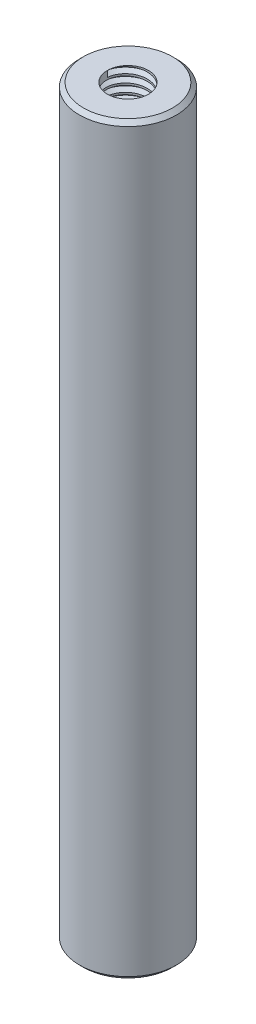
SolidWorks part; units mm, degrees
material "6061-T6 (SS)"
ref_plane "Alzado" through (0, 0, 0) normal (0, 0, 1) x (1, 0, 0)
ref_plane "Planta" through (0, 0, 0) normal (0, 1, 0) x (1, 0, 0)
ref_plane "Vista lateral" through (0, 0, 0) normal (1, 0, 0) x (0, 0, -1)
sketch "Croquis2" plane through (0, 0, 0) normal (0, 1, 0) x (1, 0, 0)
  circle A0 centre (0, 0) radius 4.7625
  dimension "D1" = 9.525
extrude "Saliente-Extruir1" add sketch "Croquis2" along normal mid plane 73.025
chamfer "Chaflán1" distance 0.3969 angle 45 2 edges at (0, -36.5125, 4.7625) (0, 36.5125, 4.7625)
sketch "Croquis3" plane through (0, 0, 0) normal (0, 1, 0) x (1, 0, 0)
  circle A0 centre (0, 0) radius 2.0193
  dimension "D1" = 4.0386
extrude "Tap Hole 1" cut sketch "Croquis3" against normal blind 19.05 from surface starting at face at (0, 36.5125, 4.3656)
extrude "Tap Hole 2" cut sketch "Croquis3<2>" along normal blind 19.05 from surface starting at face at (0, -36.5125, 4.3656)
sketch "Croquis3<2>" plane through (0, 0, 0) normal (0, 1, 0) x (1, 0, 0) same geometry as "Croquis3"
sketch "Croquis4" plane through (0, 0, 0) normal (0, 1, 0) x (1, 0, 0)
  circle A0 centre (0, 0) radius 2.4892
  dimension "D1" = 4.9784
extrude "Clearance Hole" [suppressed] cut sketch "Croquis4" against normal through all both and the other way through all
thread "Rosca1" pitch 0.7937 method cut profile "Perfil de rosca1" start angle 0, offset 0, length 0, pitch 0.7937, diameter 4.0386
ref_plane "Plano1" through (-2.0193, 36.5125, 0) normal (0, 0, 1) x (-1, 0, 0)
sketch "Perfil de rosca1" plane through (-2.0193, 36.5125, 0) normal (0, 0, 1) x (-1, 0, 0)
  line L0 (0, 0) -> (0, 0.7937) construction
  line L1 (0, 0) -> (0.4296, 0.248)
  line L2 (0.4296, 0.248) -> (0.4296, 0.3473)
  line L3 (0.4296, 0.3473) -> (0, 0.5953)
  line L4 (0.4296, 0.2977) -> (0, 0.2977) construction
  line L11 (0, 0) -> (0, 0.5953)
  point P2 (0, 0)
  dimension "Pitch" = 0.7937
  dimension "Profile_Angle" = 60
  dimension "Profile_Land" = 0.0992
  dimension "Profile_Height" = 0.4296
thread "Rosca2" pitch 0.7937 method cut profile "Perfil de rosca2" start angle 0, offset 0, length 0, pitch 0.7937, diameter 4.0386
ref_plane "Plano2" through (2.0193, -36.5125, 0) normal (0, 0, 1) x (1, 0, 0)
sketch "Perfil de rosca2" plane through (2.0193, -36.5125, 0) normal (0, 0, 1) x (1, 0, 0)
  line L0 (0, 0) -> (0, 0.7937) construction
  line L1 (0, 0) -> (0.4296, 0.248)
  line L2 (0.4296, 0.248) -> (0.4296, 0.3473)
  line L3 (0.4296, 0.3473) -> (0, 0.5953)
  line L4 (0.4296, 0.2977) -> (0, 0.2977) construction
  line L11 (0, 0) -> (0, 0.5953)
  point P2 (0, 0)
  dimension "Pitch" = 0.7937
  dimension "Profile_Angle" = 60
  dimension "Profile_Land" = 0.0992
  dimension "Profile_Height" = 0.4296
equation "\"OD\"= 0.375pulgadas"
equation "\"Largo\"= 2.875pulgadas"
equation "\"Tap Hole\"= IIF ( \"OD\" = 0.375pulgadas , 0.1590pulgadas , 0.201pulgadas )"
equation "\"Spacer Hole\"= IIF ( \"OD\" = 0.375pulgadas , 0.196pulgadas , 0.257pulgadas )"
equation "\"D1@Croquis2\"=\"OD\""
equation "\"D1@Saliente-Extruir1\"=\"Largo\""
equation "\"D1@Croquis3\"=\"Tap Hole\""
equation "\"D1@Croquis4\"=\"Spacer Hole\""
